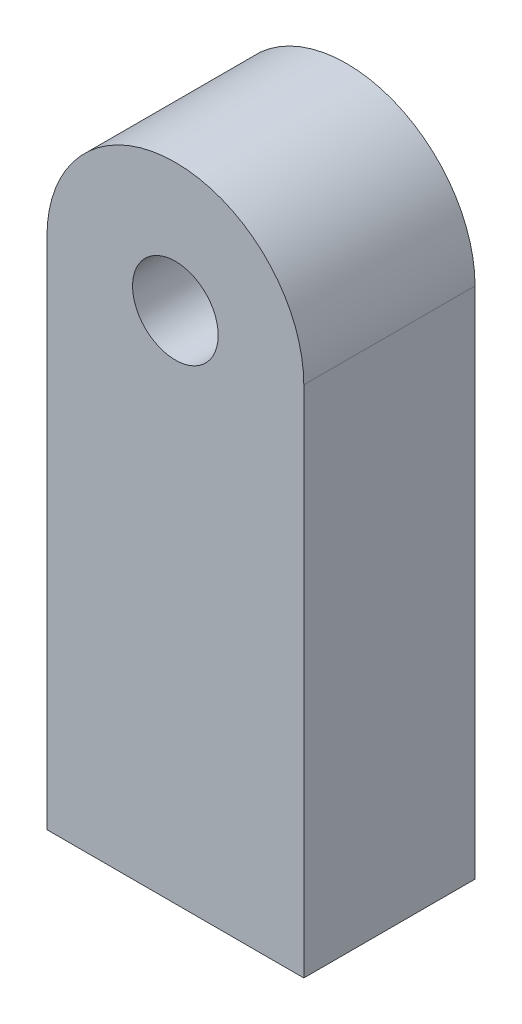
SolidWorks part; units mm, degrees
ref_plane "Front Plane" through (0, 0, 0) normal (0, 0, 1) x (1, 0, 0)
ref_plane "Top Plane" through (0, 0, 0) normal (0, 1, 0) x (1, 0, 0)
ref_plane "Right Plane" through (0, 0, 0) normal (1, 0, 0) x (0, 0, -1)
sketch "Sketch1" plane through (0, 0, 0) normal (0, 0, 1) x (1, 0, 0)
  line L0 (-60.0035, 12.6799) -> (-60.0035, 50.7799)
  line L1 (-40.9535, 50.7799) -> (-40.9535, 12.6799)
  line L2 (-40.9535, 12.6799) -> (-60.0035, 12.6799)
  arc A0 (-60.0035, 50.7799) -> (-40.9535, 50.7799) centre (-50.4785, 50.7799) cw
  circle A1 centre (-50.4785, 50.7799) radius 3.175
  dimension "D3" = 6.35
  dimension "D1" = 19.05
  dimension "D2" = 38.1
extrude "Boss-Extrude1" add sketch "Sketch1" along normal blind 6.35 and the other way blind 6.35
sketch "Sketch3" plane through (0, 12.6799, 0) normal (0, -1, 0) x (1, 0, 0)
  line L0 (-60.0035, 0) -> (-40.9535, 0)
  line L1 (-60.0035, -6.35) -> (-60.0035, 6.35) construction
  line L2 (-40.9535, -6.35) -> (-40.9535, 6.35) construction
  line L3 (-40.9535, 0) -> (-37.7785, 0)
  line L4 (-60.0035, 0) -> (-63.1785, 0)
  dimension "D1" = 3.175
  dimension "D2" = 3.175
sketch "Sketch4" plane through (0, 12.6799, 0) normal (0, -1, 0) x (1, 0, 0)
  line L0 (-60.0035, 0) -> (-40.9535, 0)
  line L1 (-60.0035, -6.35) -> (-60.0035, 6.35) construction
  line L2 (-40.9535, -6.35) -> (-40.9535, 6.35) construction
